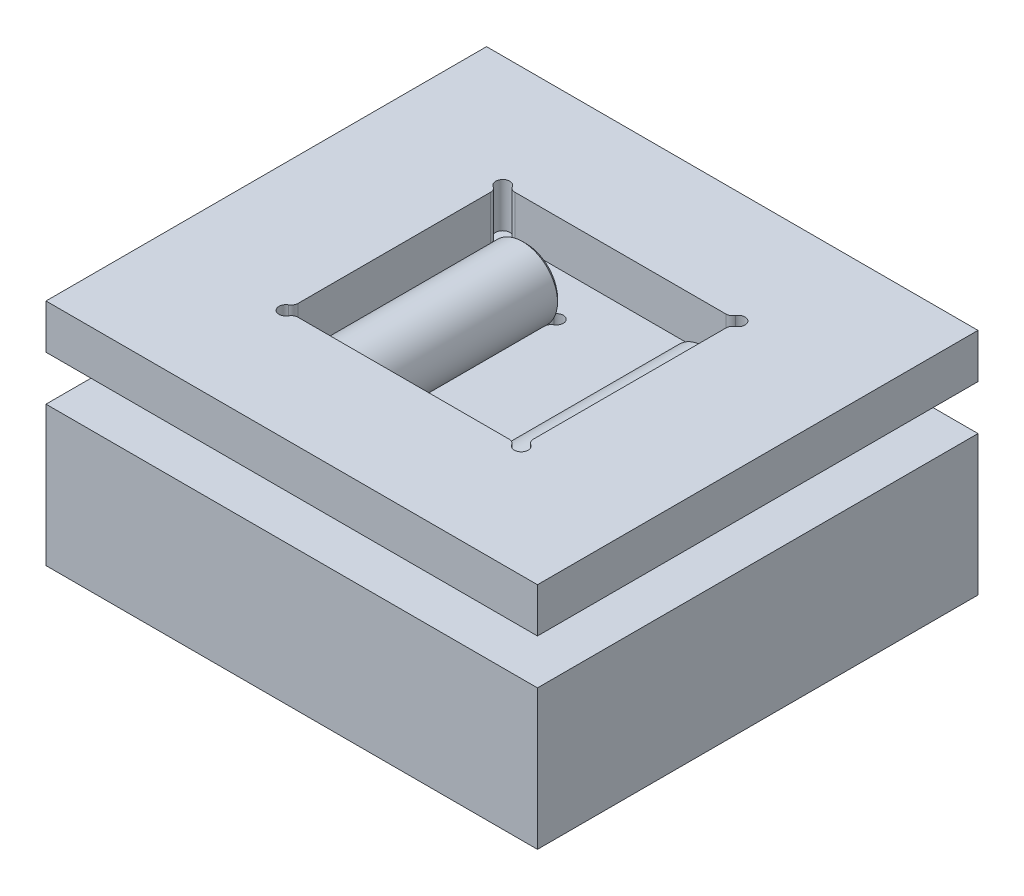
SolidWorks part; units mm, degrees
ref_plane "Front Plane" through (0, 0, 0) normal (0, 0, 1) x (1, 0, 0)
ref_plane "Top Plane" through (0, 0, 0) normal (0, 1, 0) x (1, 0, 0)
ref_plane "Right Plane" through (0, 0, 0) normal (1, 0, 0) x (0, 0, -1)
sketch "Sketch1" plane through (0, 0, 0) normal (0, 0, 1) x (1, 0, 0)
  line L0 (-6.4952, -3.75) -> (6.4952, -3.75) construction
  line L5 (-6.4952, -3.75) -> (0, 0) construction
  line L6 (-6.4952, -3.75) -> (-4.5801, -5.357) construction
  line L11 (-4.5801, -5.357) -> (4.5801, -5.357)
  line L12 (4.5801, -5.357) -> (4.5801, -15.357)
  line L13 (4.5801, -15.357) -> (-4.5801, -15.357)
  line L14 (-4.5801, -15.357) -> (-4.5801, -5.357)
  line L15 (-8.4103, -5.357) -> (-8.4103, -15.357)
  line L16 (-8.4103, -15.357) -> (-17.5705, -15.357)
  line L17 (-17.5705, -15.357) -> (-17.5705, -5.357)
  line L18 (-17.5705, -5.357) -> (-8.4103, -5.357)
  line L19 (0, -5.357) -> (0, -15.357) construction
  line L20 (17.5705, -5.357) -> (8.4103, -5.357)
  line L21 (8.4103, -15.357) -> (17.5705, -15.357)
  line L22 (8.4103, -5.357) -> (8.4103, -15.357)
  line L23 (17.5705, -15.357) -> (17.5705, -5.357)
  line L24 (-8.4103, -2.143) -> (-17.5705, -2.143)
  line L25 (-6.4952, -3.75) -> (-8.4103, -2.143) construction
  line L26 (-17.5705, -2.143) -> (-17.5705, 1.032)
  line L27 (-17.5705, 1.032) -> (-8.4103, 1.032)
  line L28 (-8.4103, 1.032) -> (-8.4103, -2.143)
  line L29 (17.5705, 1.032) -> (8.4103, 1.032)
  line L30 (17.5705, -2.143) -> (17.5705, 1.032)
  line L31 (8.4103, -2.143) -> (17.5705, -2.143)
  line L32 (8.4103, 1.032) -> (8.4103, -2.143)
  circle A1 centre (0, 0) radius 5
  circle A2 centre (6.4952, -3.75) radius 2.5
  circle A3 centre (-6.4952, -3.75) radius 2.5
  point P21 (0, -5)
  point P25 (-8.4103, -2.1957)
  dimension "D1" = 10
  dimension "D2" = 5
  dimension "D3" = 30
  dimension "D4" = 40
  dimension "D5" = 10
  dimension "D7" = 3.175
extrude "Boss-Extrude1" add sketch "Sketch1" along normal blind 7.75 contours L14 L13 L12 L11 | L21 L23 L20 L22 | L18 L15 L16 L17 | L28 L24 L26 L27 | L29 L32 L31 L30 region at (0, -10.357, 0) region at (12.9904, -10.357, 0)
sketch "Sketch2" plane through (0, 0, 7.75) normal (0, 0, 1) x (1, 0, 0)
  line L1 (-17.5705, -5.357) -> (17.5705, -5.357)
  line L2 (-17.5705, -5.357) -> (-17.5705, -15.357)
  line L3 (-17.5705, -15.357) -> (17.5705, -15.357)
  line L4 (17.5705, -5.357) -> (17.5705, -15.357)
  line L5 (-17.5705, -2.143) -> (17.5705, -2.143)
  line L6 (-17.5705, -2.143) -> (-17.5705, 1.032)
  line L7 (-17.5705, 1.032) -> (17.5705, 1.032)
  line L8 (17.5705, -2.143) -> (17.5705, 1.032)
extrude "Boss-Extrude2" add sketch "Sketch2" along normal blind 8
sketch "Sketch3" plane through (0, -5.357, 0) normal (0, 1, 0) x (1, 0, 0)
  circle A0 centre (-8.4103, -7.75) radius 0.5
  circle A1 centre (-4.5801, -7.75) radius 0.5
  circle A2 centre (4.5801, -7.75) radius 0.5
  circle A3 centre (8.4103, -7.75) radius 0.5
  dimension "D1" = 1
extrude "Cut-Extrude1" cut sketch "Sketch3" against normal through all
sketch "Sketch4" plane through (0, 1.032, 0) normal (0, 1, 0) x (1, 0, 0)
  circle A0 centre (-8.4103, -7.75) radius 0.5
  circle A1 centre (8.4103, -7.75) radius 0.5
  arc A2 (-5.0801, -7.75) -> (-4.5801, -7.25) centre (-4.5801, -7.75) ccw construction
extrude "Cut-Extrude2" cut sketch "Sketch4" against normal up to surface (3.175 mm away) up to face at (0, -2.143, 5.875)
fillet "Fillet1" radius 0.5 8 edges at (4.5801, -10.357, 7.25) (8.4103, -10.357, 7.25) (7.9103, -10.357, 7.75) (5.0801, -10.357, 7.75) (-4.5801, -10.357, 7.25) (-5.0801, -10.357, 7.75) (-7.9103, -10.357, 7.75) (-8.4103, -10.357, 7.25)
fillet "Fillet2" radius 0.5 4 edges at (8.4103, -0.5555, 7.25) (7.9103, -0.5555, 7.75) (-8.4103, -0.5555, 7.25) (-7.9103, -0.5555, 7.75)
mirror "Mirror1" about plane through (0, 0, 0) normal (0, 0, -1) of bodies 105 112
extrude "Boss-Extrude3" add sketch "Sketch1<3>" along normal mid plane 15 separate body contours A2 | A3 region at (6.4952, -3.75, 0)
sketch "Sketch1<3>" plane through (0, 0, 0) normal (0, 0, 1) x (1, 0, 0) same geometry as "Sketch1"
chamfer "Chamfer1" distance 0.25 angle 45 2 edges at (-3.9952, -3.75, -7.5) (-3.9952, -3.75, 7.5)
chamfer "Chamfer2" distance 0.25 angle 45 2 edges at (8.9952, -3.75, -7.5) (8.9952, -3.75, 7.5)
